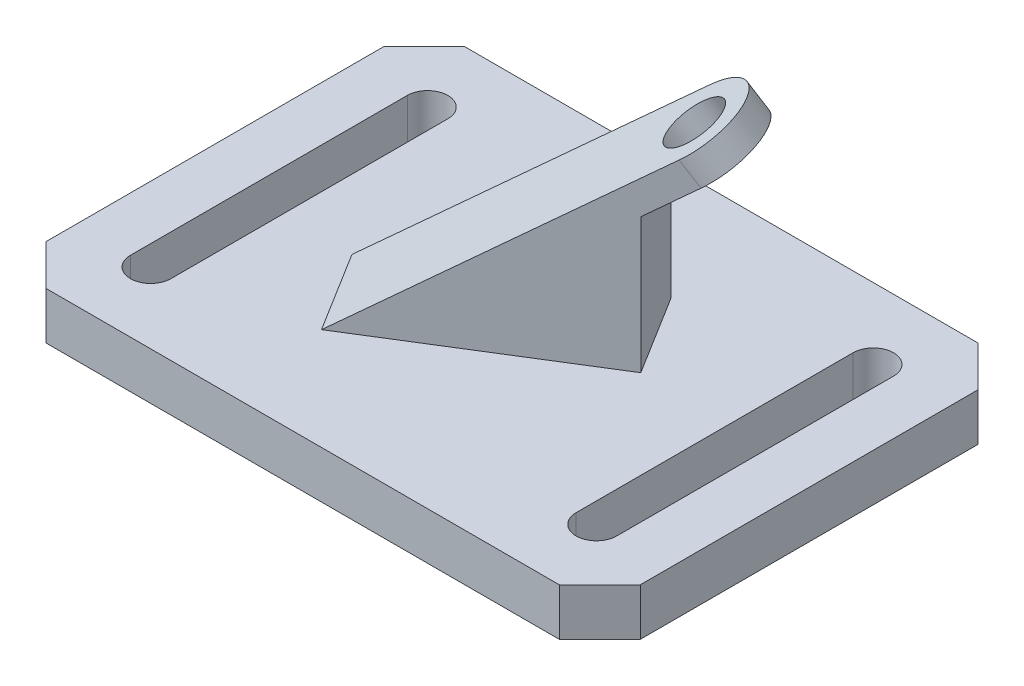
SolidWorks part; units mm, degrees
material "Alloy Steel"
ref_plane "Front Plane" through (0, 0, 0) normal (0, 0, 1) x (1, 0, 0)
ref_plane "Top Plane" through (0, 0, 0) normal (0, 1, 0) x (1, 0, 0)
ref_plane "Right Plane" through (0, 0, 0) normal (1, 0, 0) x (0, 0, -1)
sketch "Sketch1" plane through (0, 0, 0) normal (0, 1, 0) x (1, 0, 0)
  line L0 (-33, -20.5) -> (-33, 20.5) construction
  line L1 (38, -31) -> (-38, -31)
  line L2 (44, -25) -> (44, 25)
  line L3 (38, 31) -> (-38, 31)
  line L4 (-44, -25) -> (-44, 25)
  line L5 (44, -31) -> (-44, 31) construction
  line L6 (44, 31) -> (-44, -31) construction
  line L7 (-36, -20.5) -> (-36, 20.5)
  line L8 (-30, -20.5) -> (-30, 20.5)
  line L9 (33, -20.5) -> (33, 20.5) construction
  line L10 (30, -20.5) -> (30, 20.5)
  line L11 (36, -20.5) -> (36, 20.5)
  line L12 (33, 0) -> (-33, 0) construction
  line L13 (-33, -20.5) -> (33, 20.5) construction
  line L14 (-38, 31) -> (-44, 25)
  line L15 (44, 25) -> (38, 31)
  line L16 (-38, -31) -> (-44, -25)
  line L17 (44, -25) -> (38, -31)
  arc A0 (-36, -20.5) -> (-30, -20.5) centre (-33, -20.5) ccw
  arc A1 (-30, 20.5) -> (-36, 20.5) centre (-33, 20.5) ccw
  arc A2 (30, -20.5) -> (36, -20.5) centre (33, -20.5) ccw
  arc A3 (36, 20.5) -> (30, 20.5) centre (33, 20.5) ccw
  point P0 (0, 0)
  point P8 (-33, 0)
  point P14 (33, 0)
  point P25 (0, 0)
  dimension "D3" = 3
  dimension "D1" = 62
  dimension "D2" = 88
  dimension "D4" = 8
  dimension "D5" = 41
extrude "Boss-Extrude1" add sketch "Sketch1" along normal blind 7
ref_plane "Plane1" through (0, 0, 0) normal (0.5277, 0, 0.8494) x (0.8494, 0, -0.5277)
sketch "Sketch2" plane through (0, 0, 0) normal (0.5277, 0, 0.8494) x (0.8494, 0, -0.5277)
  line L0 (-38.8491, 1.3414) -> (-38.8491, 12.0026) construction
  line L2 (38.8491, 0) -> (38.8491, 17.8463) construction
  line L4 (-48.6369, 7) -> (15.9206, 7) construction
  line L8 (15.4838, 27) -> (15.4838, 7)
  line L9 (15.4838, 7) -> (-12.0439, 7)
  line L10 (15.4838, 27) -> (-12.0439, 7)
  line L11 (-12.0439, 7) -> (-18.8491, 7) construction
  line L12 (-18.8491, 7) -> (13.1326, 30.2361) construction
  line L13 (13.1326, 30.2361) -> (15.4838, 27) construction
  dimension "D1" = 4
  dimension "D2" = 36
  dimension "D3" = 20
  dimension "D4" = 20
extrude "Boss-Extrude2" add sketch "Sketch2" along normal mid plane 14 contours L8 L10 L9 region at (5.3582, 13.6667, -3.3286)
sketch "Sketch4" plane through (-6.3621, 10.3088, 3.9522) normal (-0.4993, 0.809, 0.3102) x (0.8664, 0.4662, 0.1787)
  line L0 (-13.4869, -1.5305) -> (-4.9605, -12.6345)
  line L1 (-93215.3242, -71576.3571) -> (93273.5009, 71621.0286) construction
  line L2 (-4.9605, -12.6345) -> (33.1313, 16.6146)
  line L3 (36.3316, 27.8976) -> (-9.2237, -7.0825) construction
  line L4 (-13.4869, -1.5305) -> (24.6049, 27.7187)
  line L5 (-0.2016, -8.9804) -> (-8.728, 2.1237) construction
  line L6 (26.7861, 11.7424) -> (18.2597, 22.8465) construction
  arc A0 (33.1313, 16.6146) -> (24.6049, 27.7187) centre (28.8681, 22.1667) ccw
  circle A1 centre (28.8681, 22.1667) radius 4
  dimension "D3" = 8
  dimension "D4" = 8
  dimension "D1" = 6
  dimension "D2" = 14
extrude "Boss-Extrude5" add sketch "Sketch4" along normal blind 4
